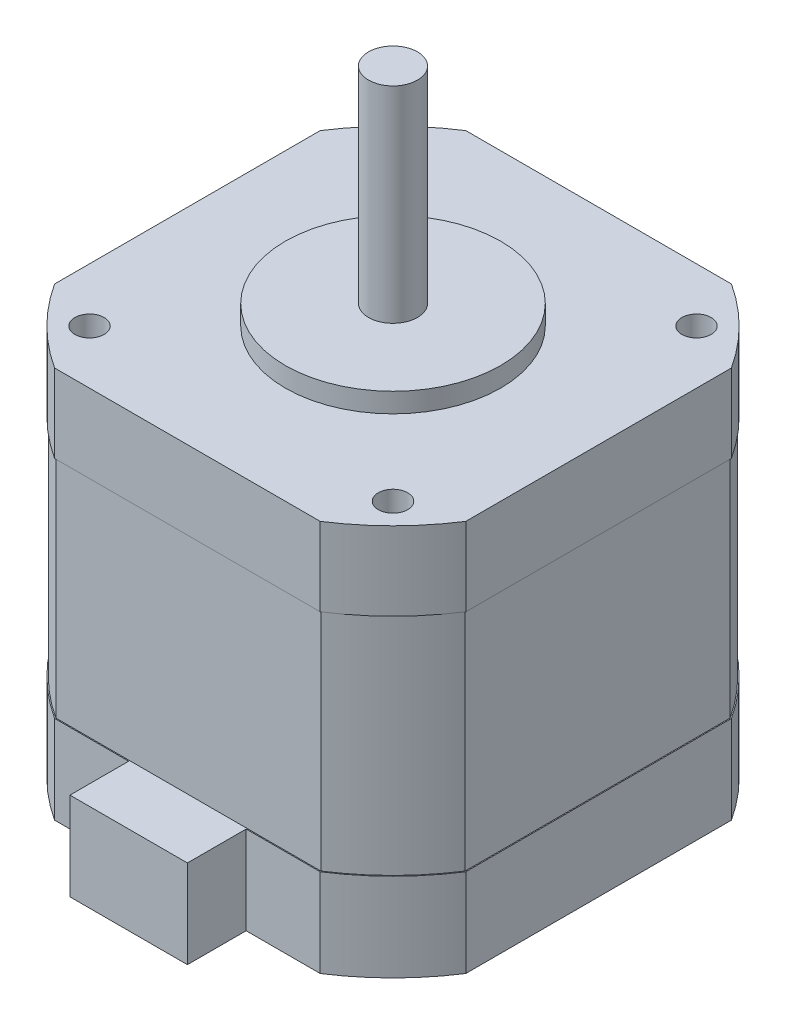
SolidWorks part; units mm, degrees
ref_plane "Спереди" through (0, 0, 0) normal (0, 0, 1) x (1, 0, 0)
ref_plane "Сверху" through (0, 0, 0) normal (0, 1, 0) x (1, 0, 0)
ref_plane "Справа" through (0, 0, 0) normal (1, 0, 0) x (0, 0, -1)
sketch "Эскиз1" plane through (0, 0, 0) normal (0, 1, 0) x (1, 0, 0)
  line L0 (-21, 21) -> (21, -21)
  line L1 (-21, -21) -> (21, -21)
  line L2 (-21, -21) -> (-21, 21)
  line L3 (-21, 21) -> (21, 21)
  line L4 (21, -21) -> (21, 21)
  line L5 (-21, -21) -> (21, 21)
  circle A0 centre (0, 0) radius 25
  dimension "D1" = 42
  dimension "D2" = 42
extrude "Бобышка-Вытянуть1" add sketch "Эскиз1" along normal blind 9 contours L5 A0 L3 L0 | L0 A0 L2 L5 | L1 A0 L0 L5 | L0 A0 L4 L5 region at (0, 0, -13.6639) region at (-13.6639, 0, 0) region at (13.6639, 0, 0) region at (0, 0, 13.6639)
sketch "Эскиз2" plane through (0, 0, 21) normal (0, 0, 1) x (1, 0, 0)
  line L0 (-13.5647, 0) -> (13.5647, 0) construction
  line L1 (-6, 0) -> (6, 0)
  line L2 (-6, 0) -> (-6, 9)
  line L3 (-6, 9) -> (6, 9)
  line L4 (6, 0) -> (6, 9)
  point P6 (0, 0)
  dimension "D1" = 12
  dimension "D2" = 9
extrude "Бобышка-Вытянуть2" add sketch "Эскиз2" along normal blind 6
sketch "Эскиз3" plane through (0, 0, 0) normal (0, 0, 1) x (1, 0, 0)
  line L0 (0, -2.1456) -> (0, 97.279) construction
sketch "Эскиз4" plane through (0, 9, 0) normal (0, 1, 0) x (1, 0, 0)
  line L0 (-21, -13.5647) -> (-21, 13.5647) construction
  line L1 (-21, -13.5647) -> (-21, 13.5647)
  line L2 (21, -13.5647) -> (21, 13.5647) construction
  line L3 (-13.5647, 21) -> (13.5647, 21) construction
  line L4 (21, -13.5647) -> (21, 13.5647)
  line L5 (-13.5647, 21) -> (13.5647, 21)
  line L6 (-13.5647, -21) -> (13.5647, -21)
  line L7 (-20.9, -13.5351) -> (-20.9, 13.5351)
  line L8 (-13.5351, 20.9) -> (13.5351, 20.9)
  line L9 (20.9, -13.5351) -> (20.9, 13.5351)
  line L10 (-13.5351, -20.9) -> (13.5351, -20.9)
  arc A0 (-21, -13.5647) -> (-13.5647, -21) centre (0, 0) ccw construction
  arc A1 (-21, -13.5647) -> (-13.5647, -21) centre (0, 0) ccw
  arc A2 (13.5647, -21) -> (21, -13.5647) centre (0, 0) ccw construction
  arc A3 (21, 13.5647) -> (13.5647, 21) centre (0, 0) ccw construction
  arc A4 (-13.5647, 21) -> (-21, 13.5647) centre (0, 0) ccw construction
  arc A5 (13.5647, -21) -> (21, -13.5647) centre (0, 0) ccw
  arc A6 (21, 13.5647) -> (13.5647, 21) centre (0, 0) ccw
  arc A7 (-13.5647, 21) -> (-21, 13.5647) centre (0, 0) ccw
  arc A8 (-13.5351, 20.9) -> (-20.9, 13.5351) centre (0, 0) ccw
  arc A9 (20.9, 13.5351) -> (13.5351, 20.9) centre (0, 0) ccw
  arc A10 (13.5351, -20.9) -> (20.9, -13.5351) centre (0, 0) ccw
  arc A11 (-20.9, -13.5351) -> (-13.5351, -20.9) centre (0, 0) ccw
  dimension "D1" = 0.1
extrude "Бобышка-Вытянуть3" add sketch "Эскиз4" along normal blind 23 contours L7 A11 L10 A10 L9 A9 L8 A8 region at (0, 9, 0)
sketch "Эскиз5" plane through (0, 32, 0) normal (0, 1, 0) x (1, 0, 0)
  line L0 (21, -13.5647) -> (21, 13.5647) construction
  line L1 (-13.5647, 21) -> (13.5647, 21) construction
  line L2 (-21, -13.5647) -> (-21, 13.5647) construction
  line L3 (21, -13.5647) -> (21, 13.5647)
  line L4 (-13.5647, 21) -> (13.5647, 21)
  line L5 (-21, -13.5647) -> (-21, 13.5647)
  line L6 (-13.5647, -21) -> (13.5647, -21)
  arc A0 (-21, -13.5647) -> (-13.5647, -21) centre (0, 0) ccw construction
  arc A1 (-21, -13.5647) -> (-13.5647, -21) centre (0, 0) ccw
  arc A2 (13.5647, -21) -> (21, -13.5647) centre (0, 0) ccw construction
  arc A3 (21, 13.5647) -> (13.5647, 21) centre (0, 0) ccw construction
  arc A4 (-13.5647, 21) -> (-21, 13.5647) centre (0, 0) ccw construction
  arc A5 (13.5647, -21) -> (21, -13.5647) centre (0, 0) ccw
  arc A6 (21, 13.5647) -> (13.5647, 21) centre (0, 0) ccw
  arc A7 (-13.5647, 21) -> (-21, 13.5647) centre (0, 0) ccw
extrude "Бобышка-Вытянуть4" add sketch "Эскиз5" along normal blind 8
sketch "Эскиз6" plane through (0, 40, 0) normal (0, 1, 0) x (1, 0, 0)
  line L0 (-28.8089, -28.8089) -> (28.8089, 28.8089) construction
  line L1 (28.1088, -28.1088) -> (-28.1088, 28.1088) construction
  line L6 (0, 0) -> (0, -21) construction
  circle A0 centre (0, 0) radius 11
  circle A2 centre (-15.5, -15.5) radius 1.5
  circle A3 centre (-15.5, 15.5) radius 1.5
  circle A4 centre (15.5, 15.5) radius 1.5
  circle A5 centre (15.5, -15.5) radius 1.5
  point P3 (28.1088, -28.1088)
  point P16 (0, 0)
  point P17 (0, 0)
  point P18 (-28.8089, -28.8089)
  point P19 (15.2336, -15.2336)
  point P20 (0, 0)
  point P21 (0, 0)
  point P23 (0, 0)
  dimension "D1" = 31
  dimension "D2" = 22
  dimension "D4" = 3
  dimension "D3" = 45
extrude "Вырез-Вытянуть1" cut sketch "Эскиз6" against normal blind 8 contours A2 | A3 | A4 | A5
extrude "Бобышка-Вытянуть5" add sketch "Эскиз6<3>" along normal blind 2 contours A0 region at (0, 40, 0)
sketch "Эскиз6<3>" plane through (0, 40, 0) normal (0, 1, 0) x (1, 0, 0) same geometry as "Эскиз6"
sketch "Эскиз7" plane through (0, 42, 0) normal (0, 1, 0) x (1, 0, 0)
  circle A0 centre (0, 0) radius 2.5
  dimension "D1" = 5
extrude "Бобышка-Вытянуть6" add sketch "Эскиз7" along normal blind 21
